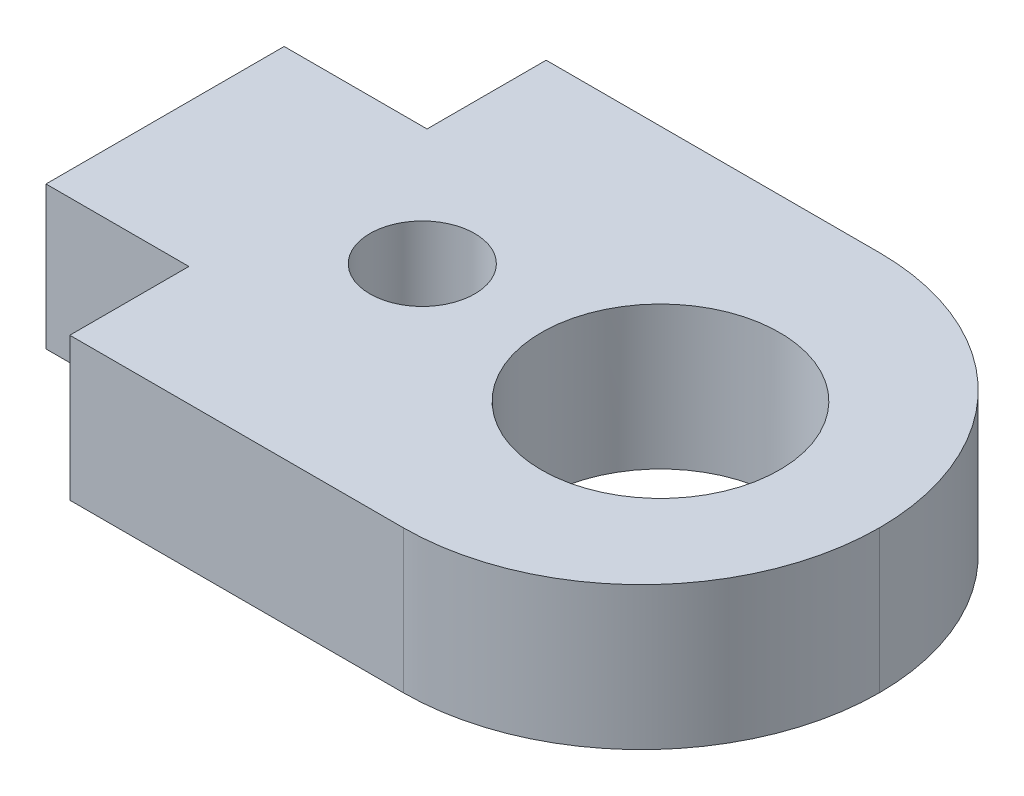
SolidWorks part; units mm, degrees
ref_plane "Alzado" through (0, 0, 0) normal (0, 0, 1) x (1, 0, 0)
ref_plane "Planta" through (0, 0, 0) normal (0, 1, 0) x (1, 0, 0)
ref_plane "Vista lateral" through (0, 0, 0) normal (1, 0, 0) x (0, 0, -1)
sketch "Croquis1" plane through (0, 0, 0) normal (0, 1, 0) x (1, 0, 0)
  line L0 (-6, 5) -> (-6, 2.5)
  line L1 (-6, -5) -> (6, -5)
  line L3 (-6, 5) -> (6, 5)
  line L4 (6, -5) -> (6, 5)
  line L5 (-6, -5) -> (6, 5) construction
  line L6 (-6, 5) -> (6, -5) construction
  line L7 (-6, 2.5) -> (-9, 2.5)
  line L8 (-9, 2.5) -> (-9, -2.5)
  line L9 (-9, -2.5) -> (-6, -2.5)
  line L10 (-6, -2.5) -> (-6, -5)
  point P0 (0, 0)
  dimension "D1" = 12
  dimension "D2" = 10
  dimension "D3" = 3
  dimension "D4" = 5
extrude "Saliente-Extruir1" add sketch "Croquis1" along normal blind 3
sketch "Croquis2" plane through (0, 3, 0) normal (0, 1, 0) x (1, 0, 0)
  line L0 (6, -5) -> (6, 5) construction
  circle A0 centre (1.4, 0) radius 2.5
  circle A1 centre (-3.6, 0) radius 1.1
  dimension "D1" = 5
  dimension "D4" = 2.2
  dimension "D2" = 4.6
  dimension "D3" = 5
extrude "Cortar-Extruir1" cut sketch "Croquis2" against normal blind 10
fillet "Redondeo1" radius 5 2 edges at (6, 1.5, -5) (6, 1.5, 5)
